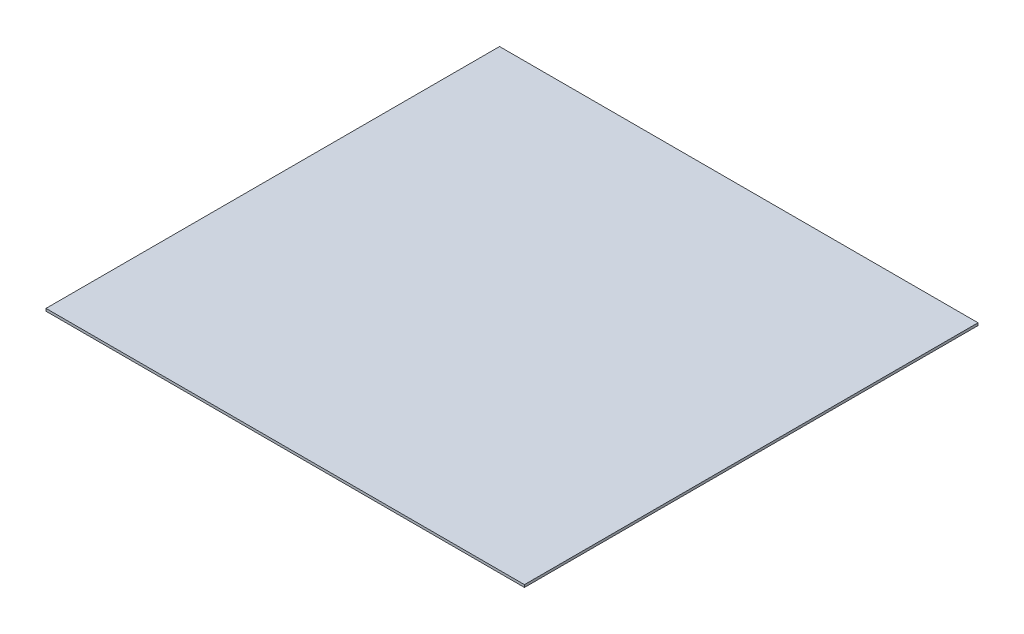
SolidWorks part; units mm, degrees
material "Acrylic (Medium-high impact)"
ref_plane "Front Plane" through (0, 0, 0) normal (0, 0, 1) x (1, 0, 0)
ref_plane "Top Plane" through (0, 0, 0) normal (0, 1, 0) x (1, 0, 0)
ref_plane "Right Plane" through (0, 0, 0) normal (1, 0, 0) x (0, 0, -1)
sketch "Sketch1" plane through (0, 0, 0) normal (0, 1, 0) x (1, 0, 0)
  line L1 (-304.8, -288.925) -> (304.8, -288.925)
  line L2 (-304.8, -288.925) -> (-304.8, 288.925)
  line L3 (-304.8, 288.925) -> (304.8, 288.925)
  line L4 (304.8, -288.925) -> (304.8, 288.925)
  line L5 (-304.8, -288.925) -> (304.8, 288.925) construction
  line L6 (-304.8, 288.925) -> (304.8, -288.925) construction
  point P0 (0, 0)
  dimension "D1" = 609.6
  dimension "D2" = 577.85
extrude "Boss-Extrude1" add sketch "Sketch1" along normal mid plane 3.175
sketch "Sketch2" plane through (0, 1.5875, 0) normal (0, 1, 0) x (1, 0, 0)
  line L0 (-304.8, -288.925) -> (-304.8, 288.925)
  line L1 (-304.8, 288.925) -> (304.8, 288.925)
  line L2 (304.8, 288.925) -> (-304.8, 288.925) construction
  line L3 (304.8, 288.925) -> (304.8, 136.525)
  line L4 (304.8, -288.925) -> (304.8, 288.925) construction
  line L5 (304.8, 136.525) -> (-152.4, 136.525)
  line L6 (-152.4, 136.525) -> (-152.4, -288.925)
  line L7 (-304.8, -288.925) -> (304.8, -288.925) construction
  line L8 (-152.4, -288.925) -> (-304.8, -288.925)
  dimension "D1" = 152.4
  dimension "D2" = 152.4
  dimension "D3" = 90
extrude "Cut-Extrude1" [suppressed] cut sketch "Sketch2" against normal through all both and the other way through all
